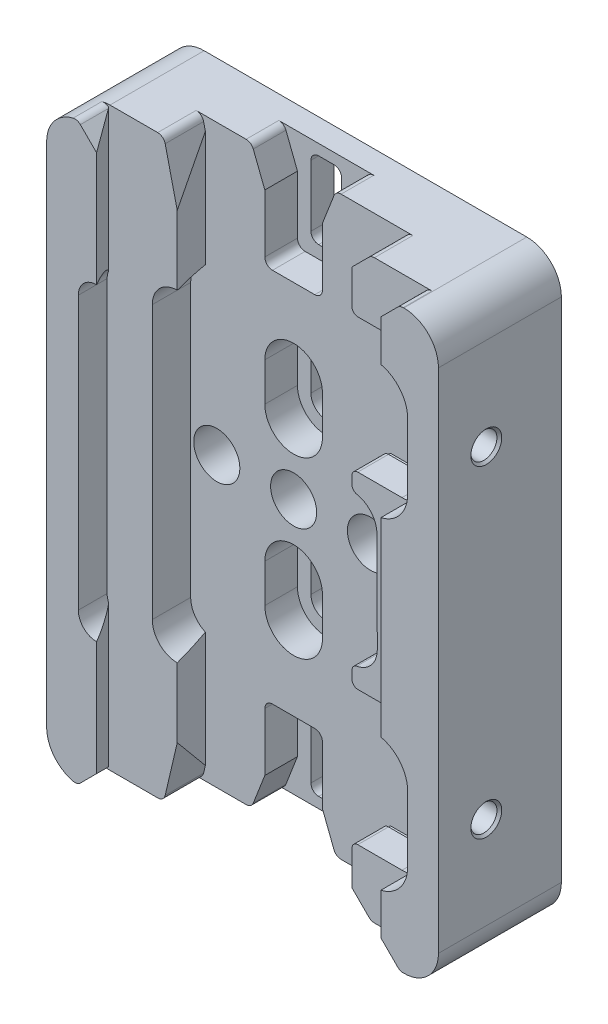
SolidWorks part; units mm, degrees
ref_plane "前视基准面" through (0, 0, 0) normal (0, 0, 1) x (1, 0, 0)
ref_plane "上视基准面" through (0, 0, 0) normal (0, 1, 0) x (1, 0, 0)
ref_plane "右视基准面" through (0, 0, 0) normal (1, 0, 0) x (0, 0, -1)
sketch "草图1" plane through (0, 0, 0) normal (0, 0, 1) x (1, 0, 0)
  line L1 (-51, -75) -> (51, -75)
  line L2 (-51, -75) -> (-51, 75)
  line L3 (-51, 75) -> (51, 75)
  line L4 (51, -75) -> (51, 75)
  line L5 (-51, -75) -> (51, 75) construction
  line L6 (-51, 75) -> (51, -75) construction
  point P0 (0, 0)
  dimension "D1" = 150
  dimension "D2" = 102
extrude "凸台-拉伸1" add sketch "草图1" along normal blind 32
sketch "草图2" plane through (0, -75, 0) normal (0, -1, 0) x (1, 0, 0)
  line L0 (-30.6612, 14.5) -> (49969.3388, 14.5) construction
  line L1 (-36.9838, 24.5) -> (49963.0162, 24.5) construction
  line L2 (-24.5, 23.1384) -> (-24.5, -49976.8616) construction
  line L3 (-38, 24.5661) -> (-38, -49975.4339) construction
  line L4 (-51, 32) -> (-51, 0) construction
  line L5 (21, 25.11) -> (21, -49974.89) construction
  line L6 (36, 24.906) -> (36, -49975.094) construction
  line L7 (-51, 0) -> (51, 0) construction
  line L8 (51, 32) -> (51, 0) construction
  line L9 (-51, 32) -> (51, 32) construction
  line L10 (21, 14.5) -> (-24.5, 14.5)
  line L11 (21, 14.5) -> (21, 24.5)
  line L12 (21, 24.5) -> (-24.5, 24.5)
  line L13 (-24.5, 14.5) -> (-24.5, 24.5)
  line L14 (36, 24.5) -> (-38, 24.5)
  line L15 (36, 24.5) -> (36, 32)
  line L16 (36, 32) -> (-38, 32)
  line L17 (-38, 24.5) -> (-38, 32)
  line L18 (-24.5, 24.5) -> (-27.1795, 14.5)
  line L19 (-27.1795, 14.5) -> (-24.5, 14.5)
  line L20 (-38, 32) -> (-42.3301, 24.5)
  line L21 (-42.3301, 24.5) -> (-38, 24.5)
  line M13 (51, 32) -> (-51, 32)
  dimension "D1" = 26.5
  dimension "D2" = 13
  dimension "D3" = 14.5
  dimension "D4" = 10
  dimension "D5" = 30
  dimension "D6" = 15
  dimension "D7" = 75
  dimension "D8" = 60
extrude "切除-拉伸1" cut sketch "草图2" against normal through all contours L20 L21 L17 | L17 L14 L12 L15 M13 | L13 L10 L11 L12 | L18 L19 L13 region at (-1.75, -75, 19.5) region at (-25.3932, -75, 17.8333) region at (-1, -75, 28.25) region at (-39.4434, -75, 27)
sketch "草图3" plane through (0, 0, 14.5) normal (0, 0, 1) x (1, 0, 0)
  line L0 (-4.2, 28.5937) -> (-4.2, -49971.4063) construction
  line L1 (0, 0) -> (50000, 0) construction
  line L2 (51, -75) -> (51, 75) construction
  line L3 (21, 75) -> (-27.1795, 75) construction
  line L4 (-4.2, 17.7) -> (-4.2, 27.7) construction
  line L5 (-4.2, -17.7) -> (-4.2, -27.7) construction
  line L6 (-8.2, 17.7) -> (-8.2, 27.7)
  line L7 (-0.2, 17.7) -> (-0.2, 27.7)
  line L8 (-6.2, 52.2) -> (-2.2, 52.2)
  line L9 (-8.2, 54.2) -> (-8.2, 70.2)
  line L10 (-6.2, 72.2) -> (-2.2, 72.2)
  line L11 (-0.2, 54.2) -> (-0.2, 70.2)
  line L12 (-8.2, 52.2) -> (-0.2, 72.2) construction
  line L13 (-8.2, 72.2) -> (-0.2, 52.2) construction
  line L14 (-8.2, -17.7) -> (-8.2, -27.7)
  line L15 (-0.2, -17.7) -> (-0.2, -27.7)
  line L16 (-8.2, -72.2) -> (-0.2, -52.2) construction
  line L17 (-8.2, -52.2) -> (-0.2, -72.2) construction
  line L18 (-0.2, -54.2) -> (-0.2, -70.2)
  line L19 (-6.2, -72.2) -> (-2.2, -72.2)
  line L20 (-8.2, -54.2) -> (-8.2, -70.2)
  line L21 (-6.2, -52.2) -> (-2.2, -52.2)
  arc A0 (-8.2, 17.7) -> (-0.2, 17.7) centre (-4.2, 17.7) ccw
  arc A1 (-0.2, 27.7) -> (-8.2, 27.7) centre (-4.2, 27.7) ccw
  circle A2 centre (-4.2, 0) radius 3.3
  arc A3 (-8.2, -17.7) -> (-0.2, -17.7) centre (-4.2, -17.7) cw
  arc A4 (-0.2, -27.7) -> (-8.2, -27.7) centre (-4.2, -27.7) cw
  arc A5 (-0.2, 70.2) -> (-2.2, 72.2) centre (-2.2, 70.2) ccw
  arc A6 (-0.2, 54.2) -> (-2.2, 52.2) centre (-2.2, 54.2) cw
  arc A7 (-6.2, 52.2) -> (-8.2, 54.2) centre (-6.2, 54.2) cw
  arc A8 (-8.2, 70.2) -> (-6.2, 72.2) centre (-6.2, 70.2) cw
  arc A9 (-8.2, -54.2) -> (-6.2, -52.2) centre (-6.2, -54.2) cw
  arc A10 (-2.2, -52.2) -> (-0.2, -54.2) centre (-2.2, -54.2) cw
  arc A11 (-0.2, -70.2) -> (-2.2, -72.2) centre (-2.2, -70.2) cw
  arc A12 (-6.2, -72.2) -> (-8.2, -70.2) centre (-6.2, -70.2) cw
  circle A13 centre (15.8, 0) radius 3.3
  circle A14 centre (-24.2, 0) radius 3.3
  point P12 (-4.2, 62.2)
  point P14 (-4.2, 22.7)
  point P24 (-4.2, 3.3)
  point P25 (-4.2, 13.7)
  point P26 (-4.2, 31.7)
  point P29 (-4.2, -22.7)
  point P38 (-4.2, -31.7)
  point P39 (-4.2, -13.7)
  point P40 (-4.2, -62.2)
  dimension "D7" = 6.6
  dimension "D10" = 2
  dimension "D14" = 20
  dimension "D1" = 55.2
  dimension "D2" = 75
  dimension "D3" = 20
  dimension "D4" = 8
  dimension "D5" = 22.7
  dimension "D6" = 10
  dimension "D8" = 144.4
  dimension "D9" = 39.5
  dimension "D11" = 63.4
  dimension "D12" = 8
  dimension "D13" = 2.8
extrude "切除-拉伸2" cut sketch "草图3" against normal through all
sketch "草图4" plane through (0, 0, 14.5) normal (0, 0, 1) x (1, 0, 0)
  circle A0 centre (15.8, 0) radius 6
  circle A1 centre (-4.2, 0) radius 6
  circle A2 centre (-24.2, 0) radius 6
  dimension "D1" = 12
  dimension "D2" = 3
extrude "切除-拉伸3" cut sketch "草图4" against normal blind 8.5
sketch "草图5" plane through (0, 0, 14.5) normal (0, 0, 1) x (1, 0, 0)
  line L0 (-31, 45.2914) -> (-31, -49954.7086) construction
  line L1 (-51, 75) -> (-51, -75) construction
  line L2 (-4.2, 0) -> (49995.8, 0) construction
  line L3 (-24.5, -35.5) -> (-24.5, 35.5) construction
  line L4 (-24.5, 75) -> (-24.5, -75) construction
  line L5 (21.0815, -12.9999) -> (21, 12.9999) construction
  line L6 (-31, -35.5) -> (-31, 35.5)
  line L7 (-18, -35.5) -> (-18, 35.5)
  line L8 (21, 75) -> (21, 2.9933) construction
  line L10 (14.5815, -13.0203) -> (14.5, 12.9796)
  line L11 (27.5815, -12.9796) -> (27.5, 13.0203)
  arc A0 (-31, -35.5) -> (-18, -35.5) centre (-24.5, -35.5) ccw
  arc A1 (-18, 35.5) -> (-31, 35.5) centre (-24.5, 35.5) ccw
  arc A2 (14.5815, -13.0203) -> (27.5815, -12.9796) centre (21.0815, -12.9999) ccw
  arc A3 (27.5, 13.0203) -> (14.5, 12.9796) centre (21, 12.9999) ccw
  point P13 (-24.5, 0)
  point P22 (21.0408, 0)
  dimension "D1" = 20
extrude "切除-拉伸4" cut sketch "草图5" along normal blind 10
sketch "草图6" plane through (0, 0, 24.5) normal (0, 0, 1) x (1, 0, 0)
  line L0 (-24.2, 0) -> (49975.8, 0) construction
  line L1 (-43, 14.8949) -> (-43, -49985.1051) construction
  line L2 (-51, 75) -> (-51, -75) construction
  line L3 (-38, -35.5) -> (-38, 35.5) construction
  line L4 (-38, 75) -> (-38, -75) construction
  line L6 (-42.75, -35.5) -> (-42.75, 35.5)
  line L7 (-33.25, -35.5) -> (-33.25, 35.5)
  arc A0 (-42.75, -35.5) -> (-33.25, -35.5) centre (-38, -35.5) ccw
  arc A1 (-33.25, 35.5) -> (-42.75, 35.5) centre (-38, 35.5) ccw
  point P13 (-38, 0)
  dimension "D1" = 8
  dimension "D2" = 9.5
extrude "切除-拉伸5" cut sketch "草图6" along normal blind 10
sketch "草图7" plane through (0, 0, 14.5) normal (0, 0, 1) x (1, 0, 0)
  line L0 (27.8174, -59.5) -> (50027.8174, -59.5) construction
  line L1 (28.2055, -24.5) -> (50028.2055, -24.5) construction
  line L2 (26.1354, 24.5) -> (50026.1354, 24.5) construction
  line L3 (26.006, 59.5) -> (50026.006, 59.5) construction
  line L4 (36, -75) -> (21, -75) construction
  line L5 (51, 75) -> (36, 75) construction
  line L6 (43, 41.5294) -> (43, -49958.4706) construction
  line L7 (51, -75) -> (51, 75) construction
  line L8 (21, 75) -> (21, 19.4999) construction
  line L9 (21, 59.5) -> (34, 59.5)
  line L10 (21, 59.5) -> (21, 24.5)
  line L11 (21, 24.5) -> (34, 24.5)
  line L12 (43, 50.5) -> (43, 33.5)
  line L13 (21, -19.4994) -> (21, -75) construction
  line L14 (21, -59.5) -> (34, -59.5)
  line L15 (21, -59.5) -> (21, -24.5)
  line L16 (21, -24.5) -> (34, -24.5)
  line L17 (43, -50.5) -> (43, -33.5)
  arc A0 (43, -50.5) -> (34, -59.5) centre (34, -50.5) cw
  arc A1 (43, -33.5) -> (34, -24.5) centre (34, -33.5) ccw
  arc A2 (43, 33.5) -> (34, 24.5) centre (34, 33.5) cw
  arc A3 (43, 50.5) -> (34, 59.5) centre (34, 50.5) ccw
  point P32 (43, -24.5)
  point P35 (43, 24.5)
  dimension "D6" = 9
  dimension "D1" = 15.5
  dimension "D2" = 35
  dimension "D3" = 15.5
  dimension "D4" = 35
  dimension "D5" = 8
extrude "切除-拉伸6" cut sketch "草图7" along normal blind 30
sketch "草图8" plane through (21, 0, 0) normal (-1, 0, 0) x (0, 0, 1)
  line L0 (16.5, 69.22) -> (16.5, -49930.78) construction
  line L1 (0, -75) -> (0, 75) construction
  line L2 (32, -42) -> (-49968, -42) construction
  line L3 (32, -50.5) -> (32, -33.5) construction
  line L4 (32, 42) -> (-49968, 42) construction
  line L5 (32, 33.5) -> (32, 50.5) construction
  line L6 (14.5, -75) -> (24.5, -75) construction
  line L7 (16.5, -23) -> (14.5, -23)
  line L8 (16.5, -23) -> (16.5, -61)
  line L9 (16.5, -61) -> (14.5, -61)
  line L10 (14.5, -23) -> (14.5, -61)
  line L12 (32, 0) -> (-49968, 0) construction
  line L13 (32, 24.725) -> (32, -24.725) construction
  line L14 (14.5, 23) -> (14.5, 61)
  line L15 (16.5, 61) -> (14.5, 61)
  line L16 (16.5, 23) -> (16.5, 61)
  line L17 (16.5, 23) -> (14.5, 23)
  point P8 (32, -42)
  point P13 (32, 42)
  point P24 (32, 0)
  dimension "D1" = 16.5
  dimension "D2" = 2
  dimension "D3" = 14
  dimension "D4" = 38
extrude "切除-拉伸7" cut sketch "草图8" against normal up to surface (22 mm away) up to face at (43, -42, 23.25)
fillet "圆角1" radius 9 4 edges at (43, 23, 15.5) (43, 61, 15.5) (43, -61, 15.5) (43, -23, 15.5)
sketch "草图9" plane through (51, 0, 0) normal (1, 0, 0) x (0, 0, -1)
  line L0 (-19.55, 42.9552) -> (-19.55, -49957.0448) construction
  line L1 (-32, 42) -> (49968, 42) construction
  line L2 (-32, 33.5) -> (-32, 50.5) construction
  line L3 (-32, -42) -> (49968, -42) construction
  line L4 (-32, -50.5) -> (-32, -33.5) construction
  line L5 (0, 12.0326) -> (0, -49987.9674) construction
  point P6 (-32, 42)
  point P11 (-32, -42)
  point P14 (-19.55, -42)
  point P15 (-19.55, 42)
  dimension "D1" = 19.55
hole_wizard "M8 螺纹孔1" positions "草图9" profile "草图10" tap size "M8" standard "GB"
sketch "草图10" plane through (51, 42, 19.55) normal (0, 1, 0) x (0, 0, -1)
  line L0 (0, 0) -> (0, 21.7929)
  line L1 (0, 21.7929) -> (3.4, 19.75)
  line L2 (3.4, 19.75) -> (3.4, 0.625)
  line L3 (3.4, 0.625) -> (4.025, 0)
  line L5 (4.025, 0) -> (0, 0)
  line L6 (-3.4, 0.625) -> (-4.025, 0) construction
  line L10 (0, 21.7929) -> (-3.4, 19.75) construction
  line L11 (0, -6.35) -> (0, 107.95) construction
  dimension "螺纹孔钻头直径" = 6.8
  dimension "螺纹孔钻头深度" = 19.75
  dimension "近端锥形沉头孔直径" = 8.05
  dimension "近端锥形沉头孔角度" = 90
  dimension "导头角度" = 118
cosmetic thread "孔螺纹线1" parameters "D1"=16, "D2"=8
cosmetic thread "孔螺纹线2" parameters "D1"=16, "D2"=8
fillet "圆角2" radius 9 4 edges at (51, -75, 16) (51, 75, 16) (-51, 75, 16) (-51, -75, 16)
sketch "草图11" plane through (0, 0, 24.5) normal (0, 0, 1) x (1, 0, 0)
  line L0 (-24.5, 60) -> (-24.5, 75)
  line L1 (-24.5, 75) -> (-24.5, 42) construction
  line L2 (21, 75) -> (-27.1795, 75) construction
  line L3 (-24.5, 75) -> (-28, 75)
  line L4 (-42, 75) -> (-24.5, 75) construction
  line L5 (-28, 75) -> (-24.5, 60)
  line L6 (-51, 66) -> (-51, -66) construction
  line L7 (-24.2, 0) -> (49975.8, 0) construction
  line L8 (-28, -75) -> (-24.5, -60)
  line L9 (-24.5, -75) -> (-28, -75)
  line L10 (-24.5, -60) -> (-24.5, -75)
  line L11 (21, 70) -> (21, 75)
  line L12 (21, 75) -> (21, 61) construction
  line L13 (21, 75) -> (26, 75)
  line L14 (36, 75) -> (21, 75) construction
  line L15 (26, 75) -> (21, 70)
  line L16 (51, -66) -> (51, 66) construction
  line L17 (26, -75) -> (21, -70)
  line L18 (21, -75) -> (26, -75)
  line L19 (21, -70) -> (21, -75)
  dimension "D1" = 15
  dimension "D2" = 25
  dimension "D3" = 23
  dimension "D4" = 5
extrude "切除-拉伸8" cut sketch "草图11" against normal up to surface (10 mm away) up to face at (15.3658, 0.0003, 14.5)
sketch "草图12" plane through (0, 0, 24.5) normal (0, 0, 1) x (1, 0, 0)
  line L0 (41, 66.2442) -> (41, -49933.7558) construction
  line L1 (42.9552, 70) -> (50042.9552, 70) construction
  line L2 (51, -66) -> (51, 66) construction
  line L3 (36, 75) -> (26, 75) construction
  line L4 (36, 75) -> (36, 70)
  line L5 (36, 75) -> (36, 59.275) construction
  line L6 (36, 70) -> (41, 75)
  line L7 (42, 75) -> (36, 75) construction
  line L8 (41, 75) -> (36, 75)
  line L9 (-38, 75) -> (-38, 70)
  line L10 (-38, 75) -> (-38, 40.25) construction
  line L11 (-38, 70) -> (-43, 75)
  line L12 (-38, 75) -> (-42, 75) construction
  line L13 (-43, 75) -> (-38, 75)
  line L14 (-38, -75) -> (-38, -70)
  line L15 (-38, -40.25) -> (-38, -75) construction
  line L16 (-38, -70) -> (-43, -75)
  line L17 (-42, -75) -> (-38, -75) construction
  line L18 (-43, -75) -> (-38, -75)
  line L19 (36, -75) -> (36, -70)
  line L20 (36, -59.275) -> (36, -75) construction
  line L21 (36, -70) -> (41, -75)
  line L22 (36, -75) -> (42, -75) construction
  line L23 (41, -75) -> (36, -75)
  dimension "D1" = 10
  dimension "D2" = 5
  dimension "D3" = 5
  dimension "D4" = 5
  dimension "D5" = 5
  dimension "D6" = 5
  dimension "D7" = 5
  dimension "D8" = 5
  dimension "D9" = 5
extrude "切除-拉伸9" cut sketch "草图12" along normal up to surface (7.5 mm away) contours L23 L21 L19 | L16 L18 L14 | L6 L8 L4 | L13 L11 L9 region at (37.6667, 73.3333, 24.5) region at (-39.6667, 73.3333, 24.5) region at (-39.6667, -73.3333, 24.5) region at (37.6667, -73.3333, 24.5) up to face at (-42.9195, 0, 32)
fillet "圆角3" radius 2 8 edges at (-28, 75, 19.5) (-42.9497, 74.9497, 28.25) (26, 75, 19.5) (41, 75, 28.25) (-28, -75, 19.5) (-42.9497, -74.9497, 28.25) (26, -75, 19.5) (41, -75, 28.25)
sketch "草图13" plane through (0, 0, 14.5) normal (0, 0, 1) x (1, 0, 0)
  line L0 (-4.2, -17.7) -> (-4.2, -27.7) construction
  line L1 (3.3, -17.7) -> (3.3, -27.7)
  line L2 (-11.7, -17.7) -> (-11.7, -27.7)
  line L3 (-4.2, 27.7) -> (-4.2, 17.7) construction
  line L4 (3.3, 27.7) -> (3.3, 17.7)
  line L5 (-11.7, 27.7) -> (-11.7, 17.7)
  line L6 (26.8284, 75) -> (-29.5871, 75) construction
  line L8 (-11.7, 66) -> (-11.7, 48.9)
  line L9 (-11.7, 48.9) -> (3.3, 48.9)
  line L10 (3.3, 66) -> (3.3, 48.9)
  line L11 (-11.418, 75) -> (3.3, 48.9) construction
  line L12 (-11.7, 48.9) -> (3.018, 75) construction
  line L13 (-0.2, 62.2) -> (-50000.2, 62.2) construction
  line L14 (-0.2, 54.2) -> (-0.2, 70.2) construction
  line L15 (-4.2, 52.2) -> (-4.2, 50052.2) construction
  line L16 (-6.2, 52.2) -> (-2.2, 52.2) construction
  line L17 (-15.2, 75) -> (6.8, 75)
  line L18 (-15.2, 75) -> (-11.7, 66)
  line L19 (6.8, 75) -> (3.3, 66)
  line L20 (-4.2, 0) -> (49995.8, 0) construction
  line L21 (-11.7, -48.9) -> (3.018, -75) construction
  line L22 (-11.418, -75) -> (3.3, -48.9) construction
  line L23 (6.8, -75) -> (3.3, -66)
  line L24 (-15.2, -75) -> (-11.7, -66)
  line L25 (-15.2, -75) -> (6.8, -75)
  line L26 (3.3, -66) -> (3.3, -48.9)
  line L27 (-11.7, -48.9) -> (3.3, -48.9)
  line L28 (-11.7, -66) -> (-11.7, -48.9)
  arc A0 (3.3, -17.7) -> (-11.7, -17.7) centre (-4.2, -17.7) ccw
  arc A1 (-11.7, -27.7) -> (3.3, -27.7) centre (-4.2, -27.7) ccw
  arc A2 (3.3, 27.7) -> (-11.7, 27.7) centre (-4.2, 27.7) ccw
  arc A3 (-11.7, 17.7) -> (3.3, 17.7) centre (-4.2, 17.7) ccw
  point P4 (-4.2, -22.7)
  point P9 (-4.2, 22.7)
  point P18 (-4.2, 62.2)
  point P29 (-0.2, 62.2)
  point P34 (-4.2, 52.2)
  point P39 (-4.2, 75)
  point P51 (-4.2, -75)
  point P52 (-4.2, -62.2)
  dimension "D1" = 26.1
  dimension "D2" = 15
  dimension "D3" = 9
extrude "切除-拉伸10" cut sketch "草图13" against normal up to surface (8.5 mm away) up to face at (-18.2, 0, 6)
fillet "圆角4" radius 2 8 edges at (-15.2, -75, 10.25) (6.8, -75, 10.25) (6.8, 75, 10.25) (-15.2, 75, 10.25) (3.3, 48.9, 10.25) (-11.7, 48.9, 10.25) (-11.7, -48.9, 10.25) (3.3, -48.9, 10.25)
fillet "圆角5" radius 1.5 6 edges at (21, -59.5, 20.5) (21, -24.5, 20.5) (21, -19.4994, 19.5) (21, 19.4999, 19.5) (21, 24.5, 20.5) (21, 59.5, 20.5)
sketch "草图14" plane through (0, 0, 32) normal (0, 0, 1) x (1, 0, 0)
  line L1 (-66.1148, 80.7351) -> (64.6916, 80.7351)
  line L2 (-66.1148, 80.7351) -> (-66.1148, -83.4521)
  line L3 (-66.1148, -83.4521) -> (64.6916, -83.4521)
  line L4 (64.6916, 80.7351) -> (64.6916, -83.4521)
extrude "切除-拉伸11" [suppressed] cut sketch "草图14" against normal up to surface (26 mm away)
